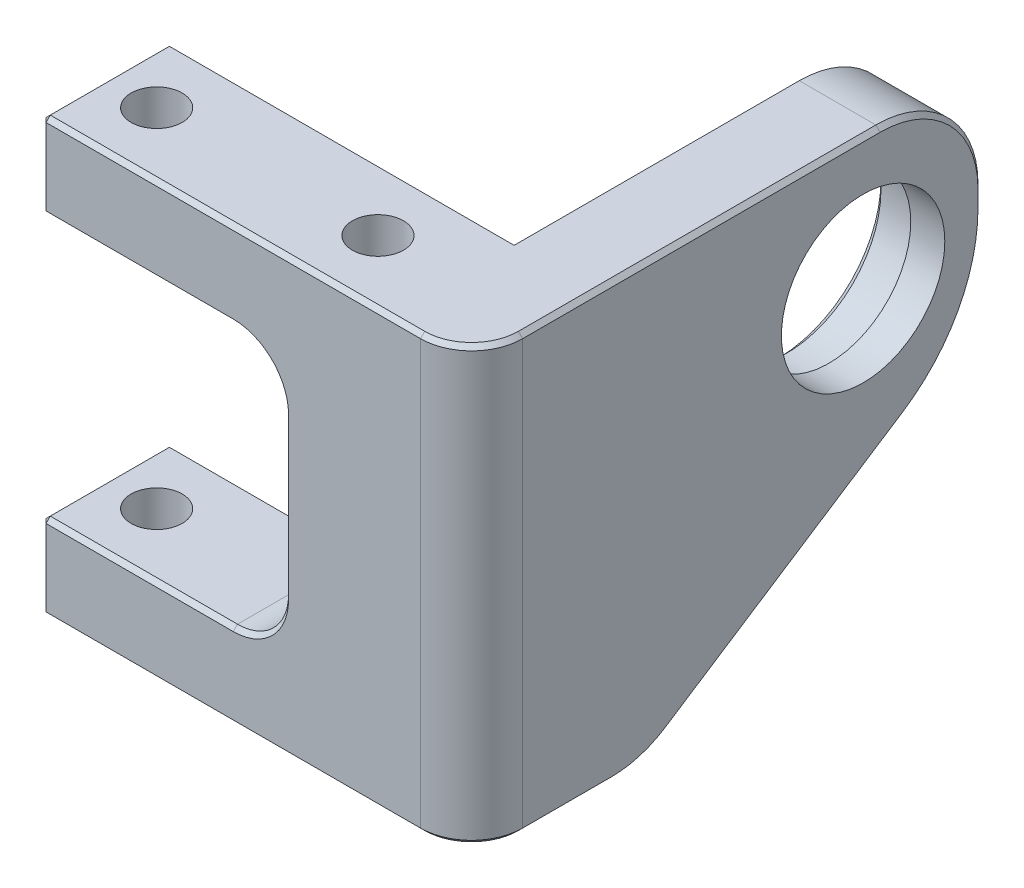
SolidWorks part; units mm, degrees
ref_plane "Front Plane" through (0, 0, 0) normal (0, 0, 1) x (1, 0, 0)
ref_plane "Top Plane" through (0, 0, 0) normal (0, 1, 0) x (1, 0, 0)
ref_plane "Right Plane" through (0, 0, 0) normal (1, 0, 0) x (0, 0, -1)
sketch "Sketch2" plane through (0, 0, 0) normal (0, 1, 0) x (1, 0, 0)
  line L0 (0, 7.5) -> (50.5, 7.5)
  line L5 (50.5, 7.5) -> (50.5, -52.5)
  line L6 (50.5, -52.5) -> (40.5, -52.5)
  line L7 (40.5, -52.5) -> (40.5, -7.5)
  line L8 (40.5, -7.5) -> (0, -7.5)
  line L9 (0, -7.5) -> (0, 7.5)
  point P5 (0, 0)
  dimension "D1" = 15
  dimension "D2" = 10
  dimension "D3" = 40.5
  dimension "D4" = 45
extrude "Boss-Extrude1" add sketch "Sketch2" along normal blind 50.8 contours L5 L6 L7 L8 L9 L0
sketch "Sketch3" plane through (40.5, 0, 0) normal (-1, 0, 0) x (0, 0, 1)
  line L0 (7.5, 50.8) -> (7.5, 0) construction
  line L1 (52.5, 50.8) -> (7.5, 50.8) construction
  circle A0 centre (38.5, 35.4) radius 11.1
  dimension "D2" = 22.2
  dimension "D1" = 31
  dimension "D3" = 15.4
extrude "Cut-Extrude1" cut sketch "Sketch3" against normal blind 6
sketch "Sketch4" plane through (46.5, 0, 0) normal (-1, 0, 0) x (0, 0, 1)
  circle A2 centre (38.5, 35.4) radius 9.6
  circle A3 centre (38.5, 35.4) radius 9.6
  dimension "D1" = 1.5
extrude "Cut-Extrude2" cut sketch "Sketch4" against normal through all
sketch "Sketch5" plane through (40.5, 0, 0) normal (-1, 0, 0) x (0, 0, 1)
  line L0 (12.5, 0) -> (52.5, 0)
  line L1 (52.5, 0) -> (7.5, 0) construction
  line L2 (52.5, 0) -> (52.5, 26)
  line L3 (52.5, 50.8) -> (52.5, 0) construction
  line L4 (52.5, 26) -> (12.5, 0)
  dimension "D1" = 26
  dimension "D2" = 40
extrude "Cut-Extrude3" cut sketch "Sketch5" against normal through all
fillet "Fillet1" radius 20 1 edges at (45.5, 26, 52.5)
fillet "Fillet2" radius 12 1 edges at (45.5, 50.8, 52.5)
sketch "Sketch6" plane through (0, 50.8, 0) normal (0, 1, 0) x (1, 0, 0)
  line L0 (0, -7.5) -> (0, 7.5) construction
  circle A0 centre (6, 0) radius 3
  circle A1 centre (32, 0) radius 3
  dimension "D1" = 6
  dimension "D2" = 6
  dimension "D3" = 26
extrude "Cut-Extrude4" cut sketch "Sketch6" against normal through all
sketch "Sketch7" plane through (0, 0, 7.5) normal (0, 0, 1) x (1, 0, 0)
  line L0 (0, 50.8) -> (0, 0) construction
  line L1 (0, 40.8) -> (28.5, 40.8)
  line L2 (0, 40.8) -> (0, 10)
  line L3 (0, 10) -> (28.5, 10)
  line L4 (28.5, 40.8) -> (28.5, 10)
  line L5 (40.5, 50.8) -> (0, 50.8) construction
  line L6 (40.5, 20.0848) -> (40.5, 0) construction
  line L7 (40.5, 0) -> (0, 0) construction
  dimension "D1" = 10
  dimension "D2" = 12
  dimension "D3" = 10
extrude "Cut-Extrude5" cut sketch "Sketch7" against normal through all
fillet "Fillet3" radius 6 2 edges at (28.5, 40.8, 0) (28.5, 10, 0)
fillet "Fillet4" radius 6 1 edges at (50.5, 25.4, -7.5)
fillet "Fillet5" radius 12 1 edges at (45.5, 0, 12.5)
chamfer "Chamfer1" distance 0.5 angle 45 38 edges at (11.25, 10, -7.5) (11.25, 40.8, -7.5) (26.7426, 11.7574, -7.5) (26.7426, 39.0426, -7.5) (28.5, 25.4, -7.5) (40.5, 50.8, 24) (11.25, 40.8, 7.5) (40.5, 47.2853, 48.9853) (26.7426, 39.0426, 7.5) (40.5, 37.8269, 52.5) (28.5, 25.4, 7.5) (40.5, 27.3142, 50.0783) (26.7426, 11.7574, 7.5) (0, 5, 7.5) (40.5, 11.0118, 29.4412) (40.5, 0, 8.2214) (20.25, 0, 7.5) (0, 0, 0) (11.25, 10, 7.5) (0, 10, 0) (0, 5, -7.5) (22.25, 0, -7.5) (50.5, 0, 3.7214) (50.5, 11.0118, 29.4412) (50.5, 27.3142, 50.0783) (50.5, 37.8269, 52.5) (50.5, 47.2853, 48.9853) (50.5, 50.8, 19.5) (0, 45.8, -7.5) (22.25, 50.8, -7.5) (0, 50.8, 0) (0, 40.8, 0) (0, 45.8, 7.5) (20.25, 50.8, 7.5) (48.7426, 0, -5.7426) (48.7426, 50.8, -5.7426) (50.5, 0.4949, 12.3533) (40.5, 0.4949, 12.3533)
chamfer "Chamfer2" distance 1 angle 45 1 edges at (40.5, 35.4, 49.6)
mirror "Mirror1" about plane through (0, 50.8, -7.5) normal (0, 0, -1) of bodies 106
delete or keep bodies "Body-Delete/Keep 2" type delete bodies bodies 106
